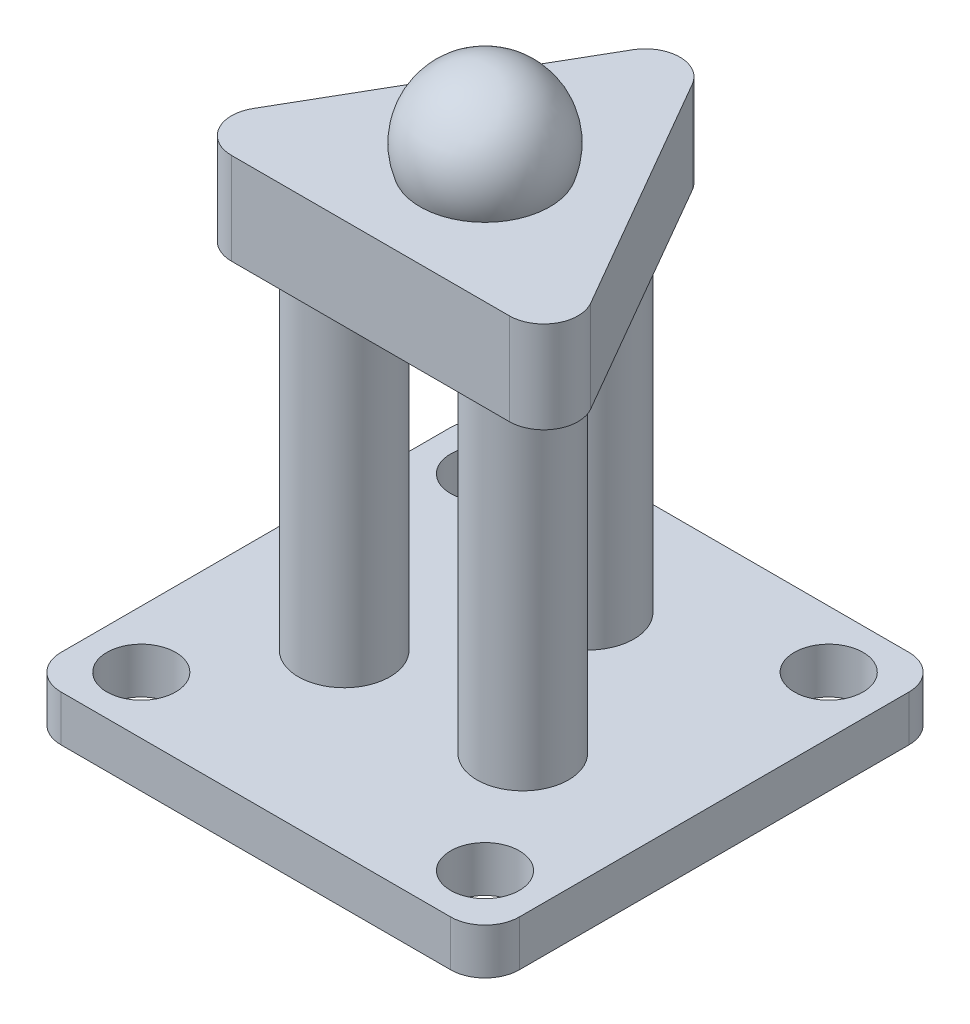
SolidWorks part; units mm, degrees
ref_plane "前视基准面" through (0, 0, 0) normal (0, 0, 1) x (1, 0, 0)
ref_plane "上视基准面" through (0, 0, 0) normal (0, 1, 0) x (1, 0, 0)
ref_plane "右视基准面" through (0, 0, 0) normal (1, 0, 0) x (0, 0, -1)
other "Configuration Table"
sketch "草图1" plane through (0, 0, 0) normal (0, 1, 0) x (1, 0, 0)
  line L1 (-8.5, -10) -> (8.5, -10)
  line L2 (-10, -8.5) -> (-10, 8.5)
  line L3 (-8.5, 10) -> (8.5, 10)
  line L4 (10, -8.5) -> (10, 8.5)
  line L5 (-10, -10) -> (10, 10) construction
  line L6 (-10, 10) -> (10, -10) construction
  line L11 (-7.5, -7.5) -> (7.5, 7.5) construction
  line L12 (-7.5, 7.5) -> (7.5, -7.5) construction
  circle A0 centre (7.5, 7.5) radius 1.5
  circle A1 centre (-7.5, 7.5) radius 1.5
  circle A2 centre (-7.5, -7.5) radius 1.5
  circle A3 centre (7.5, -7.5) radius 1.5
  arc A4 (8.5, 10) -> (10, 8.5) centre (8.5, 8.5) cw
  arc A5 (10, -8.5) -> (8.5, -10) centre (8.5, -8.5) cw
  arc A6 (-8.5, -10) -> (-10, -8.5) centre (-8.5, -8.5) cw
  arc A7 (-10, 8.5) -> (-8.5, 10) centre (-8.5, 8.5) cw
  point P0 (0, 0)
  point P6 (0, 0)
  dimension "D1" = 1.5
extrude "凸台-拉伸1" add sketch "草图1" along normal blind 2
sketch "草图2" plane through (0, 2, 0) normal (0, 1, 0) x (1, 0, 0)
  circle A0 centre (0, 4.5) radius 2
  circle A1 centre (3.8971, -2.25) radius 2
  circle A2 centre (-3.8971, -2.25) radius 2
  point P11 (0, 0)
  dimension "D1" = 3
extrude "凸台-拉伸2" add sketch "草图2" along normal blind 15
sketch "草图4" plane through (0, 17, 0) normal (0, 1, 0) x (1, 0, 0)
  line L1 (-1.299, 7.75) -> (-7.3612, -2.75)
  line L2 (-6.0622, -5) -> (6.0622, -5)
  line L3 (7.3612, -2.75) -> (1.299, 7.75)
  circle A0 centre (0, 0) radius 5 construction
  arc A1 (7.3612, -2.75) -> (6.0622, -5) centre (6.0622, -3.5) cw
  arc A2 (-6.0622, -5) -> (-7.3612, -2.75) centre (-6.0622, -3.5) cw
  arc A3 (1.299, 7.75) -> (-1.299, 7.75) centre (0, 7) ccw
  dimension "D1" = 1.5
extrude "凸台-拉伸3" add sketch "草图4" along normal blind 4
sketch "草图6" plane through (0, 0, 0) normal (0, 1, 0) x (1, 0, 0)
  line L1 (-10, -10) -> (10, -10)
  line L2 (-10, -10) -> (-10, 10)
  line L3 (-10, 10) -> (10, 10)
  line L4 (10, -10) -> (10, 10)
  line L5 (-10, -10) -> (10, 10) construction
  line L6 (-10, 10) -> (10, -10) construction
  point P0 (0, 0)
sketch "草图7" plane through (0, 0, 0) normal (0, 0, 1) x (1, 0, 0)
  line L0 (0, 19) -> (0, 25)
  line L1 (0, 25) -> (0, 19)
  circle A2 centre (0, 22) radius 3
revolve "旋转4" add sketch "草图7" angle 360 about L0 region at (1.2732, 22, 0)
